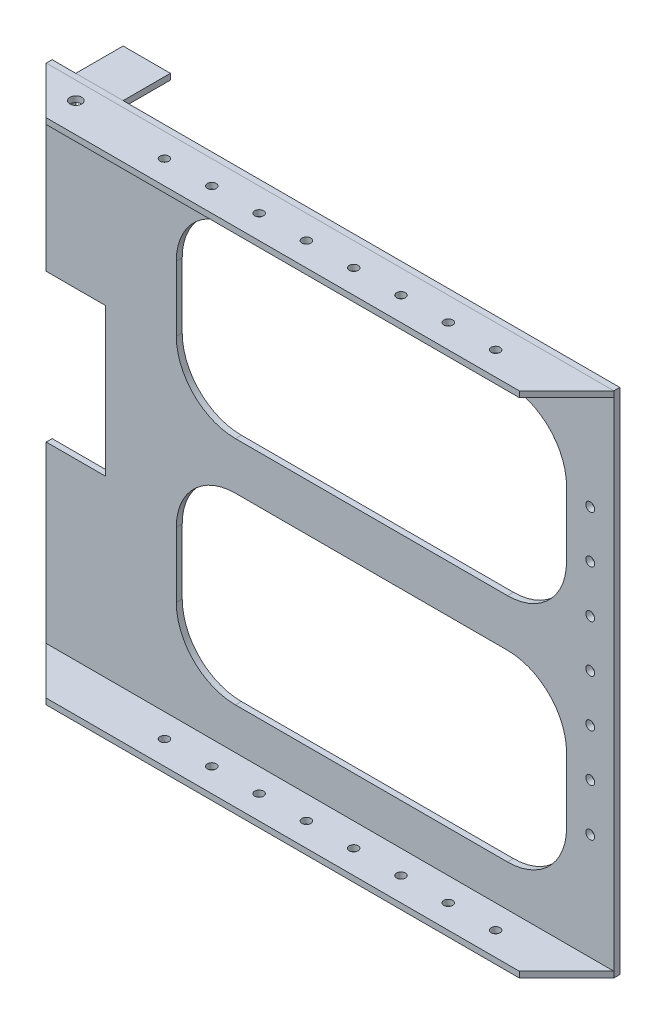
SolidWorks part; units mm, degrees
ref_plane "Front Plane" through (0, 0, 0) normal (0, 0, 1) x (1, 0, 0)
ref_plane "Top Plane" through (0, 0, 0) normal (0, 1, 0) x (1, 0, 0)
ref_plane "Right Plane" through (0, 0, 0) normal (1, 0, 0) x (0, 0, -1)
sketch "Sketch1" plane through (0, 0, 0) normal (0, 0, 1) x (1, 0, 0)
  line L1 (0, 0) -> (304.8, 0)
  line L2 (0, 0) -> (0, 273.05)
  line L3 (0, 273.05) -> (304.8, 273.05)
  line L4 (304.8, 0) -> (304.8, 273.05)
  dimension "D1" = 273.05
  dimension "D2" = 304.8
extrude "Boss-Extrude1" add sketch "Sketch1" along normal blind 3.175
sketch "Sketch2" plane through (0, 0, 3.175) normal (0, 0, 1) x (1, 0, 0)
  line L0 (0, 273.05) -> (0, 0) construction
  line L1 (101.6, 247.65) -> (247.65, 247.65)
  line L2 (69.85, 215.9) -> (69.85, 180.975)
  line L3 (101.6, 149.225) -> (247.65, 149.225)
  line L4 (279.4, 215.9) -> (279.4, 180.975)
  line L5 (101.6, 123.825) -> (247.65, 123.825)
  line L6 (69.85, 92.075) -> (69.85, 57.15)
  line L7 (101.6, 25.4) -> (247.65, 25.4)
  line L8 (279.4, 92.075) -> (279.4, 57.15)
  line L9 (0, 176.2125) -> (31.75, 176.2125)
  line L10 (0, 176.2125) -> (0, 96.8375)
  line L11 (0, 96.8375) -> (31.75, 96.8375)
  line L12 (31.75, 176.2125) -> (31.75, 96.8375)
  line L13 (304.8, 0) -> (304.8, 273.05) construction
  line L14 (304.8, 273.05) -> (0, 273.05) construction
  line L15 (0, 0) -> (304.8, 0) construction
  line L16 (-17.1716, 136.525) -> (403.4647, 136.525) construction
  arc A0 (101.6, 123.825) -> (69.85, 92.075) centre (101.6, 92.075) ccw
  arc A1 (69.85, 57.15) -> (101.6, 25.4) centre (101.6, 57.15) ccw
  arc A2 (247.65, 25.4) -> (279.4, 57.15) centre (247.65, 57.15) ccw
  arc A3 (247.65, 123.825) -> (279.4, 92.075) centre (247.65, 92.075) cw
  arc A4 (69.85, 180.975) -> (101.6, 149.225) centre (101.6, 180.975) ccw
  arc A5 (247.65, 149.225) -> (279.4, 180.975) centre (247.65, 180.975) ccw
  arc A6 (247.65, 247.65) -> (279.4, 215.9) centre (247.65, 215.9) cw
  arc A7 (101.6, 247.65) -> (69.85, 215.9) centre (101.6, 215.9) ccw
  dimension "D11" = 31.75
  dimension "D1" = 25.4
  dimension "D2" = 25.4
  dimension "D3" = 25.4
  dimension "D4" = 25.4
  dimension "D5" = 25.4
  dimension "D6" = 38.1
  dimension "D7" = 38.1
  dimension "D8" = 31.75
  dimension "D9" = 79.375
  dimension "D10" = 136.525
  dimension "D12" = 39.6875
extrude "Cut-Extrude1" cut sketch "Sketch2" against normal blind 3.175 normal cut yes
sketch "Sketch4" plane through (0, 0, 3.175) normal (0, 0, 1) x (1, 0, 0)
  line L0 (304.8, 0) -> (304.8, 273.05) construction
  line L1 (0, 273.05) -> (304.8, 273.05)
  line L2 (0, 273.05) -> (0, 269.875)
  line L3 (0, 269.875) -> (304.8, 269.875)
  line L4 (304.8, 273.05) -> (304.8, 269.875)
  dimension "D1" = 3.175
sketch "Sketch5" plane through (0, 0, 3.175) normal (0, 0, 1) x (1, 0, 0)
  line L1 (0, 273.05) -> (304.8, 273.05)
  line L2 (0, 273.05) -> (0, 269.875)
  line L3 (0, 269.875) -> (304.8, 269.875)
  line L4 (304.8, 273.05) -> (304.8, 269.875)
base flange "Base-Flange1" sketch "Sketch5" thickness 25.4 reverse thickness direction yes parameters "D1"=0.7366
chamfer "Chamfer1" distance 25.4 angle 45 2 edges at (0, 271.4625, 28.575) (304.8, 271.4625, 28.575)
sketch "Sketch10" plane through (0, 0, 3.175) normal (0, 0, 1) x (1, 0, 0)
  line L0 (304.8, 0) -> (304.8, 273.05) construction
  line L1 (0, 0) -> (304.8, 0)
  line L2 (0, 0) -> (0, 3.175)
  line L3 (0, 3.175) -> (304.8, 3.175)
  line L4 (304.8, 0) -> (304.8, 3.175)
  dimension "D1" = 3.175
base flange "Base-Flange2" sketch "Sketch10" thickness 25.4 reverse thickness direction yes parameters "D1"=0.7366
chamfer "Chamfer2" distance 25.4 angle 45 2 edges at (0, 1.5875, 28.575) (304.8, 1.5875, 28.575)
sketch "Sketch13" plane through (0, 273.05, 0) normal (0, 1, 0) x (1, 0, 0)
  line L1 (279.4, -28.575) -> (25.4, -28.575) construction
  circle A0 centre (25.4, -12.7) radius 3.175
  dimension "D3" = 6.35
  dimension "D1" = 25.4
  dimension "D2" = 15.875
extrude "Cut-Extrude4" cut sketch "Sketch13" against normal blind 3.175 normal cut yes
sketch "Sketch14" plane through (0, 0, 0) normal (0, 0, -1) x (-1, 0, 0)
  line L0 (-304.8, 273.05) -> (0, 273.05) construction
  line L1 (-38.1, 273.05) -> (-12.7, 273.05)
  line L2 (-38.1, 273.05) -> (-38.1, 269.875)
  line L3 (-38.1, 269.875) -> (-12.7, 269.875)
  line L4 (-12.7, 273.05) -> (-12.7, 269.875)
  line L5 (0, 273.05) -> (0, 176.2125) construction
  dimension "D1" = 3.175
  dimension "D2" = 25.4
  dimension "D3" = 12.7
base flange "Base-Flange3" sketch "Sketch14" thickness 25.4 reverse thickness direction yes parameters "D1"=0.7366
sketch "Sketch18" plane through (0, 0, 0) normal (0, 0, -1) x (-1, 0, 0)
  line L1 (-38.1, 269.875) -> (-12.7, 269.875)
  line L2 (-38.1, 269.875) -> (-38.1, 257.175)
  line L3 (-38.1, 257.175) -> (-12.7, 257.175)
  line L4 (-12.7, 269.875) -> (-12.7, 257.175)
  dimension "D1" = 25.4
  dimension "D2" = 12.7
extrude "Cut-Extrude5" cut sketch "Sketch18" against normal blind 3.175 normal cut yes
sketch "Sketch19" plane through (0, 273.05, 0) normal (0, 1, 0) x (1, 0, 0)
  line L0 (-49.272, -15.875) -> (322.0215, -15.875) construction
  line L1 (279.4, -28.575) -> (25.4, -28.575) construction
  circle A0 centre (76.2, -15.875) radius 2.3813
  circle A1 centre (101.6, -15.875) radius 2.3813
  circle A2 centre (127, -15.875) radius 2.3813
  circle A3 centre (152.4, -15.875) radius 2.3813
  circle A4 centre (177.8, -15.875) radius 2.3813
  circle A5 centre (203.2, -15.875) radius 2.3813
  circle A6 centre (228.6, -15.875) radius 2.3813
  circle A7 centre (254, -15.875) radius 2.3813
  dimension "D8" = 4.7625
  dimension "D1" = 12.7
  dimension "D2" = 25.4
  dimension "D3" = 25.4
  dimension "D4" = 25.4
  dimension "D5" = 25.4
  dimension "D6" = 25.4
  dimension "D7" = 76.2
  dimension "D9" = 25.4
  dimension "D10" = 25.4
extrude "Cut-Extrude7" cut sketch "Sketch19" against normal through all normal cut yes
sketch "Sketch20" plane through (0, 0, 0) normal (0, 0, -1) x (-1, 0, 0)
  line L0 (-292.1, 281.8115) -> (-292.1, -48.566) construction
  line L1 (-304.8, 0) -> (-304.8, 273.05) construction
  line L2 (-356.7906, 136.525) -> (75.1704, 136.525) construction
  line L3 (0, 273.05) -> (-304.8, 273.05) construction
  circle A0 centre (-292.1, 136.525) radius 2.3813
  circle A1 centre (-292.1, 161.925) radius 2.3813
  circle A2 centre (-292.1, 187.325) radius 2.3813
  circle A3 centre (-292.1, 212.725) radius 2.3813
  circle A4 centre (-292.1, 111.125) radius 2.3813
  circle A5 centre (-292.1, 85.725) radius 2.3813
  circle A6 centre (-292.1, 60.325) radius 2.3813
  dimension "D3" = 4.7625
  dimension "D1" = 12.7
  dimension "D2" = 136.525
  dimension "D4" = 25.4
  dimension "D5" = 50.8
  dimension "D6" = 25.4
  dimension "D7" = 25.4
  dimension "D8" = 25.4
  dimension "D9" = 50.8
extrude "Cut-Extrude8" cut sketch "Sketch20" against normal blind 50.8 normal cut yes
sketch "Bend-Lines1" [suppressed] plane through (0, 0, 0) normal (0, 1, 0) x (1, 0, 0)
sketch "Bounding-Box1" [suppressed] plane through (0, 0, 0) normal (0, 1, 0) x (1, 0, 0)
sheet metal parameters "Sheet-Metal3" thickness 25.4 parameters "D1"=0.7366
flat pattern "Flat-Pattern3" [suppressed]
sketch "Bend-Lines2" plane through (0, 0, 0) normal (0, 1, 0) x (1, 0, 0)
sketch3d "Bounding-Box2" [suppressed]
  line L0 (0, 269.875, 0) -> (-304.8, 269.875, 0) construction
  line L1 (0, 273.05, 0) -> (-304.8, 273.05, 0) construction
  line L2 (0, 269.875, 0) -> (0, 273.05, 0) construction
  line L3 (-304.8, 269.875, 0) -> (-304.8, 273.05, 0) construction
sheet metal parameters "Sheet-Metal4" thickness 25.4 parameters "D1"=0.7366
flat pattern "Flat-Pattern4"
sketch "Bend-Lines3" plane through (0, 0, 0) normal (0, 1, 0) x (1, 0, 0)
sketch3d "Bounding-Box3" [suppressed]
  line L0 (0, 0, 0) -> (-304.8, 0, 0) construction
  line L1 (0, 3.175, 0) -> (-304.8, 3.175, 0) construction
  line L2 (0, 0, 0) -> (0, 3.175, 0) construction
  line L3 (-304.8, 0, 0) -> (-304.8, 3.175, 0) construction
sheet metal parameters "Sheet-Metal5" thickness 25.4 parameters "D1"=0.7366
flat pattern "Flat-Pattern3"
sketch "Bend-Lines2" plane through (0, 0, 0) normal (0, 1, 0) x (1, 0, 0)
sketch3d "Bounding-Box2" [suppressed]
  line L0 (0, 269.875, 0) -> (-304.8, 269.875, 0) construction
  line L1 (0, 273.05, 0) -> (-304.8, 273.05, 0) construction
  line L2 (0, 269.875, 0) -> (0, 273.05, 0) construction
  line L3 (-304.8, 269.875, 0) -> (-304.8, 273.05, 0) construction
sheet metal parameters "Sheet-Metal6" thickness 25.4 parameters "D1"=0.7366
flat pattern "Flat-Pattern6"
sketch "Bend-Lines4" plane through (0, 0, 0) normal (0, 1, 0) x (1, 0, 0)
sketch3d "Bounding-Box4" [suppressed]
  line L0 (12.7, 269.875, 0) -> (38.1, 269.875, 0) construction
  line L1 (12.7, 273.05, 0) -> (38.1, 273.05, 0) construction
  line L2 (12.7, 269.875, 0) -> (12.7, 273.05, 0) construction
  line L3 (38.1, 269.875, 0) -> (38.1, 273.05, 0) construction
sheet metal parameters "Sheet-Metal9" thickness 25.4 parameters "D1"=0.7366
flat pattern "Flat-Pattern4"
sketch "Bend-Lines3" plane through (0, 0, 0) normal (0, 1, 0) x (1, 0, 0)
sketch3d "Bounding-Box3" [suppressed]
  line L0 (0, 0, 0) -> (-304.8, 0, 0) construction
  line L1 (0, 3.175, 0) -> (-304.8, 3.175, 0) construction
  line L2 (0, 0, 0) -> (0, 3.175, 0) construction
  line L3 (-304.8, 0, 0) -> (-304.8, 3.175, 0) construction
sheet metal parameters "Sheet-Metal10" thickness 25.4 parameters "D1"=0.7366
flat pattern "Flat-Pattern3"
sketch "Bend-Lines2" plane through (0, 0, 0) normal (0, 1, 0) x (1, 0, 0)
sketch3d "Bounding-Box2" [suppressed]
  line L0 (0, 269.875, 0) -> (-304.8, 269.875, 0) construction
  line L1 (0, 273.05, 0) -> (-304.8, 273.05, 0) construction
  line L2 (0, 269.875, 0) -> (0, 273.05, 0) construction
  line L3 (-304.8, 269.875, 0) -> (-304.8, 273.05, 0) construction
